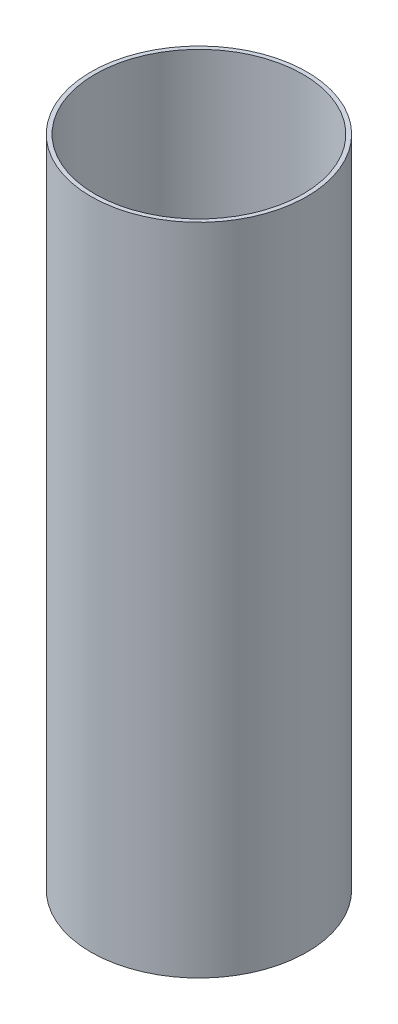
SolidWorks part; units mm, degrees
ref_plane "Front Plane" through (0, 0, 0) normal (0, 0, 1) x (1, 0, 0)
ref_plane "Top Plane" through (0, 0, 0) normal (0, 1, 0) x (1, 0, 0)
ref_plane "Right Plane" through (0, 0, 0) normal (1, 0, 0) x (0, 0, -1)
sketch "Sketch1" plane through (0, 0, 0) normal (0, 1, 0) x (1, 0, 0)
  circle A0 centre (0, 0) radius 38.1
  circle A1 centre (0, 0) radius 39.6
  dimension "D1" = 76.2
  dimension "D2" = 1.5
extrude "Boss-Extrude1" add sketch "Sketch1" along normal blind 240
